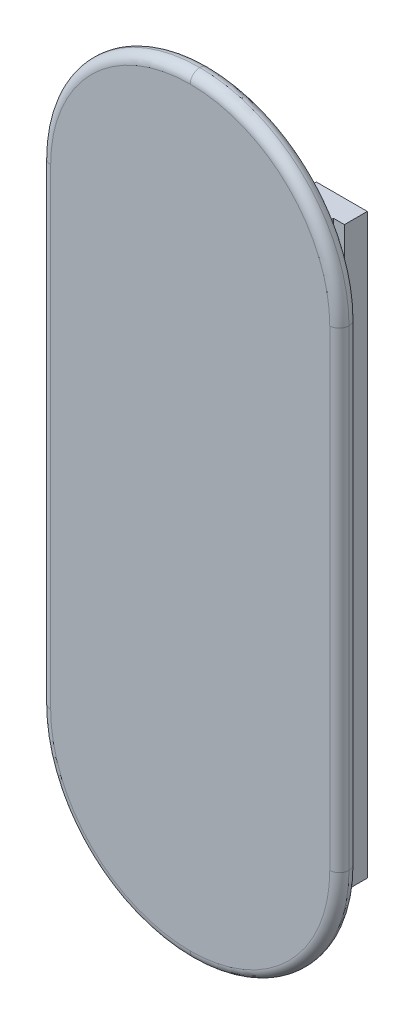
SolidWorks part; units mm, degrees
ref_plane "Front Plane" through (0, 0, 0) normal (0, 0, 1) x (1, 0, 0)
ref_plane "Top Plane" through (0, 0, 0) normal (0, 1, 0) x (1, 0, 0)
ref_plane "Right Plane" through (0, 0, 0) normal (1, 0, 0) x (0, 0, -1)
sketch "Sketch1" plane through (0, 0, 0) normal (0, 0, 1) x (1, 0, 0)
  line L1 (15.5, -40) -> (-15.5, -40)
  line L2 (15.5, -40) -> (15.5, 40)
  line L3 (15.5, 40) -> (-15.5, 40)
  line L4 (-15.5, -40) -> (-15.5, 40)
  line L5 (15.5, -40) -> (-15.5, 40) construction
  line L6 (15.5, 40) -> (-15.5, -40) construction
  point P0 (0, 0)
  dimension "D1" = 31
  dimension "D2" = 80
extrude "Boss-Extrude1" add sketch "Sketch1" along normal blind 2
fillet "Fillet1" radius 15.5 4 edges at (-15.5, 40, 1) (15.5, -40, 1) (-15.5, -40, 1) (15.5, 40, 1)
sketch "Sketch2" plane through (0, 0, 0) normal (0, 1, 0) x (1, 0, 0)
  line L0 (0, 0) -> (0, 7.8725) construction
  line L1 (-9, 0) -> (-9, 2.375) construction
  line L2 (0, 0) -> (-15.5, 0) construction
  line L3 (-9, 2.375) -> (-9, 4.75) construction
  line L4 (-7.5, 0) -> (-10.5, 0)
  line L5 (-7.5, 0) -> (-7.5, 2.375)
  line L6 (-7.5, 4.75) -> (-10.5, 4.75)
  line L7 (-10.5, 0) -> (-10.5, 2.375)
  line L8 (-7.5, 0) -> (-10.5, 4.75) construction
  line L9 (-7.5, 4.75) -> (-10.5, 0) construction
  line L10 (-10.5, 2.375) -> (-11.65, 2.375)
  line L11 (-6.35, 2.375) -> (-7.5, 2.375)
  line L12 (-6.35, 2.375) -> (-6.35, 4.75)
  line L13 (-6.35, 4.75) -> (-11.65, 4.75)
  line L14 (-11.65, 2.375) -> (-11.65, 4.75)
  line L15 (-6.35, 2.375) -> (-11.65, 4.75) construction
  line L16 (-6.35, 4.75) -> (-11.65, 2.375) construction
  line L17 (10.5, 0) -> (10.5, 2.375)
  line L18 (7.5, 0) -> (10.5, 0)
  line L19 (7.5, 0) -> (7.5, 2.375)
  line L20 (6.35, 2.375) -> (7.5, 2.375)
  line L21 (6.35, 2.375) -> (6.35, 4.75)
  line L22 (6.35, 4.75) -> (11.65, 4.75)
  line L23 (11.65, 2.375) -> (11.65, 4.75)
  line L24 (10.5, 2.375) -> (11.65, 2.375)
  point P11 (-9, 3.5625)
  dimension "D1" = 4.75
  dimension "D2" = 2.375
  dimension "D3" = 3
  dimension "D4" = 5.3
  dimension "D5" = 7.5
extrude "Boss-Extrude2" add sketch "Sketch2" along normal blind 30 and the other way blind 30 contours L14 L10 L7 L4 L5 L11 L12 L13 L6 | L17 L24 L23 L22 L21 L20 L19 L18 region at (-9, 0, -2.7041) region at (9, 0, -2.7041)
fillet "Fillet3" radius 1 12 edges at (-15.5, 0, 0) (-10.9602, -35.4602, 0) (10.9602, -35.4602, 0) (15.5, 0, 0) (10.9602, 35.4602, 0) (10.9602, 35.4602, 2) (15.5, 0, 2) (10.9602, -35.4602, 2) (-10.9602, -35.4602, 2) (-15.5, 0, 2) (-10.9602, 35.4602, 0) (-10.9602, 35.4602, 2)
